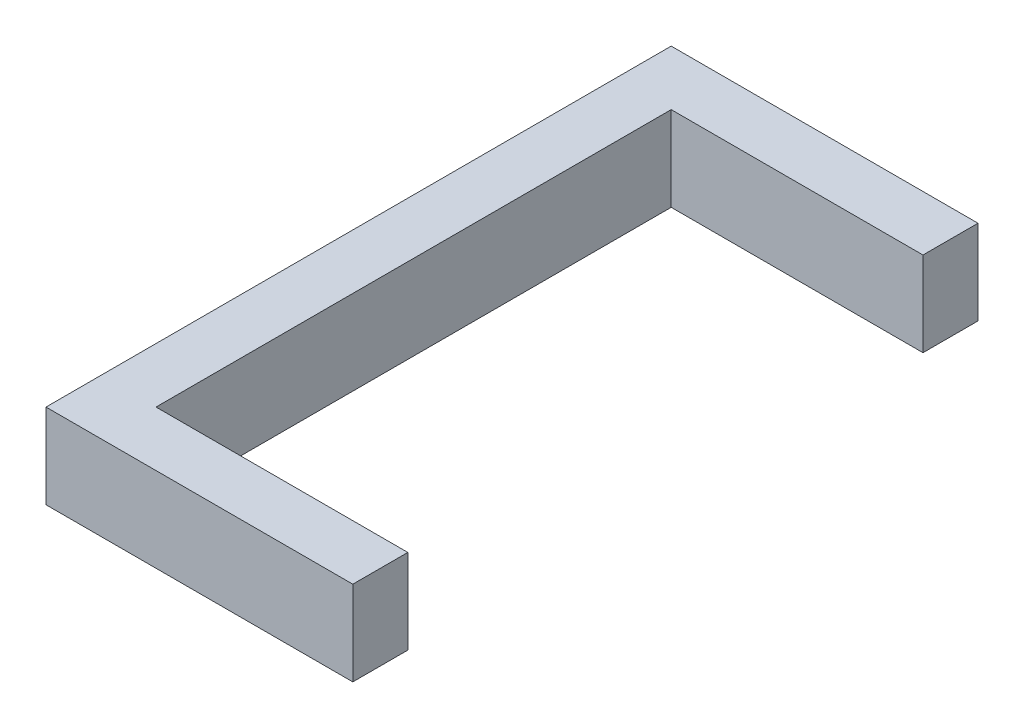
SolidWorks part; units mm, degrees
ref_plane "Front" through (0, 0, 0) normal (0, 0, 1) x (1, 0, 0)
ref_plane "Top" through (0, 0, 0) normal (0, 1, 0) x (1, 0, 0)
ref_plane "Right" through (0, 0, 0) normal (1, 0, 0) x (0, 0, -1)
sketch "Sketch1" plane through (0, 0, 0) normal (0, 1, 0) x (1, 0, 0)
  line L0 (0, 0) -> (0, 938.149)
  line L1 (0, 938.149) -> (460.375, 938.149)
  line L2 (460.375, 938.149) -> (460.375, 855.599)
  line L3 (460.375, 855.599) -> (82.55, 855.599)
  line L4 (82.55, 855.599) -> (82.55, 82.55)
  line L5 (82.55, 82.55) -> (460.375, 82.55)
  line L6 (460.375, 82.55) -> (460.375, 0)
  line L7 (460.375, 0) -> (0, 0)
  dimension "D1" = 773.049
  dimension "D2" = 82.55
  dimension "D3" = 377.825
  dimension "D4" = 82.55
extrude "Boss-Extrude1" add sketch "Sketch1" along normal blind 127
